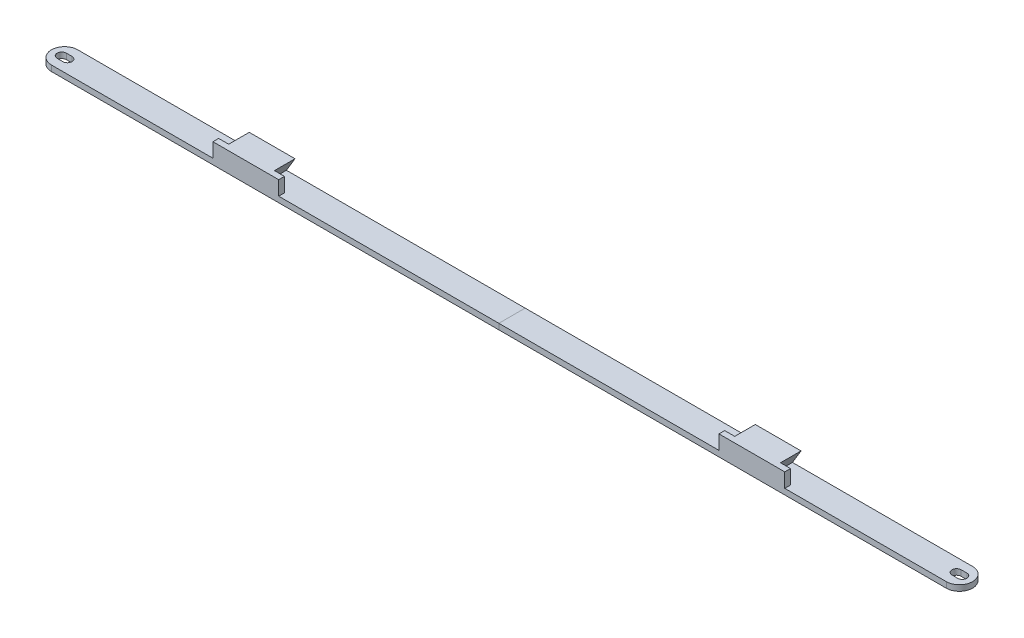
SolidWorks part; units mm, degrees
material "PLA"
ref_plane "Спереди" through (0, 0, 0) normal (0, 0, 1) x (1, 0, 0)
ref_plane "Сверху" through (0, 0, 0) normal (0, 1, 0) x (1, 0, 0)
ref_plane "Справа" through (0, 0, 0) normal (1, 0, 0) x (0, 0, -1)
sketch "Эскиз1" plane through (0, 0, 0) normal (0, 1, 0) x (1, 0, 0)
  line L0 (0, 0) -> (0, 44955.4742) construction
  line L1 (0, 0) -> (-44955.4742, 0) construction
  line L2 (-156.5, 4.6) -> (156.5, 4.6)
  line L3 (156.5, -4.6) -> (-156.5, -4.6)
  line L4 (-155.5, 0) -> (-157.5, 0) construction
  line L5 (-155.5, -1.6) -> (-157.5, -1.6)
  line L6 (-155.5, 1.6) -> (-157.5, 1.6)
  line L7 (155.5, 0) -> (157.5, 0) construction
  line L8 (155.5, -1.6) -> (157.5, -1.6)
  line L9 (155.5, 1.6) -> (157.5, 1.6)
  arc A2 (-156.5, 4.6) -> (-156.5, -4.6) centre (-156.5, 0) ccw
  arc A3 (156.5, 4.6) -> (156.5, -4.6) centre (156.5, 0) cw
  arc A4 (-155.5, -1.6) -> (-155.5, 1.6) centre (-155.5, 0) ccw
  arc A5 (-157.5, 1.6) -> (-157.5, -1.6) centre (-157.5, 0) ccw
  arc A6 (155.5, -1.6) -> (155.5, 1.6) centre (155.5, 0) cw
  arc A7 (157.5, 1.6) -> (157.5, -1.6) centre (157.5, 0) cw
  point P7 (-156.5, 0)
  point P17 (-152.1966, 1.3157)
  point P21 (156.5, 0)
  point P26 (0, 0)
  point P27 (0, 0)
  point P28 (0, 0)
  point P29 (0, 0)
  point P30 (-155.2363, 5.8637)
  point P31 (0, 0)
  dimension "D2" = 2
  dimension "D1" = 1.6
  dimension "D4" = 2
  dimension "D3" = 313
extrude "Бобышка-Вытянуть1" add sketch "Эскиз1" along normal blind 2
sketch "Эскиз2" plane through (0, 0, 4.6) normal (0, 0, 1) x (1, 0, 0)
  line L0 (0, 0) -> (0, 50000) construction
  line L1 (-156.5, 0) -> (156.5, 0) construction
  line L3 (-156.5, 2) -> (156.5, 2) construction
  line L7 (-93.5, 2) -> (-96.5, 7)
  line L8 (-96.5, 7) -> (-80.5, 7)
  line L9 (-80.5, 7) -> (-83.5, 2)
  line L10 (-83.5, 2) -> (-93.5, 2)
  line L11 (80.5, 7) -> (83.5, 2)
  line L12 (96.5, 7) -> (80.5, 7)
  line L13 (93.5, 2) -> (96.5, 7)
  line L14 (83.5, 2) -> (93.5, 2)
  point P4 (0, 0)
  point P12 (0, 2)
  dimension "D1" = 16
  dimension "D2" = 5
  dimension "D3" = 10
  dimension "D4" = 83.5
extrude "Бобышка-Вытянуть3" add sketch "Эскиз2" against normal up to surface (9.2 mm away) up to face at (0, 1, -4.6)
sketch "Эскиз3" plane through (0, 0, 4.6) normal (0, 0, 1) x (1, 0, 0)
  line L0 (-156.5, 0) -> (156.5, 0) construction
  line L1 (-100, 0) -> (-77, 0)
  line L2 (-100, 0) -> (-100, 7)
  line L3 (-100, 7) -> (-77, 7)
  line L4 (-77, 0) -> (-77, 7)
  line L6 (0, 0) -> (0, 50000) construction
  line L7 (100, 7) -> (77, 7)
  line L8 (77, 0) -> (77, 7)
  line L9 (100, 0) -> (77, 0)
  line L10 (100, 0) -> (100, 7)
  point P12 (0, 0)
  dimension "D1" = 77
  dimension "D2" = 23
extrude "Бобышка-Вытянуть4" add sketch "Эскиз3" against normal blind 2
split "Разделить1" trim tools "Справа" bodies to split 106 resulting bodies 107 108
